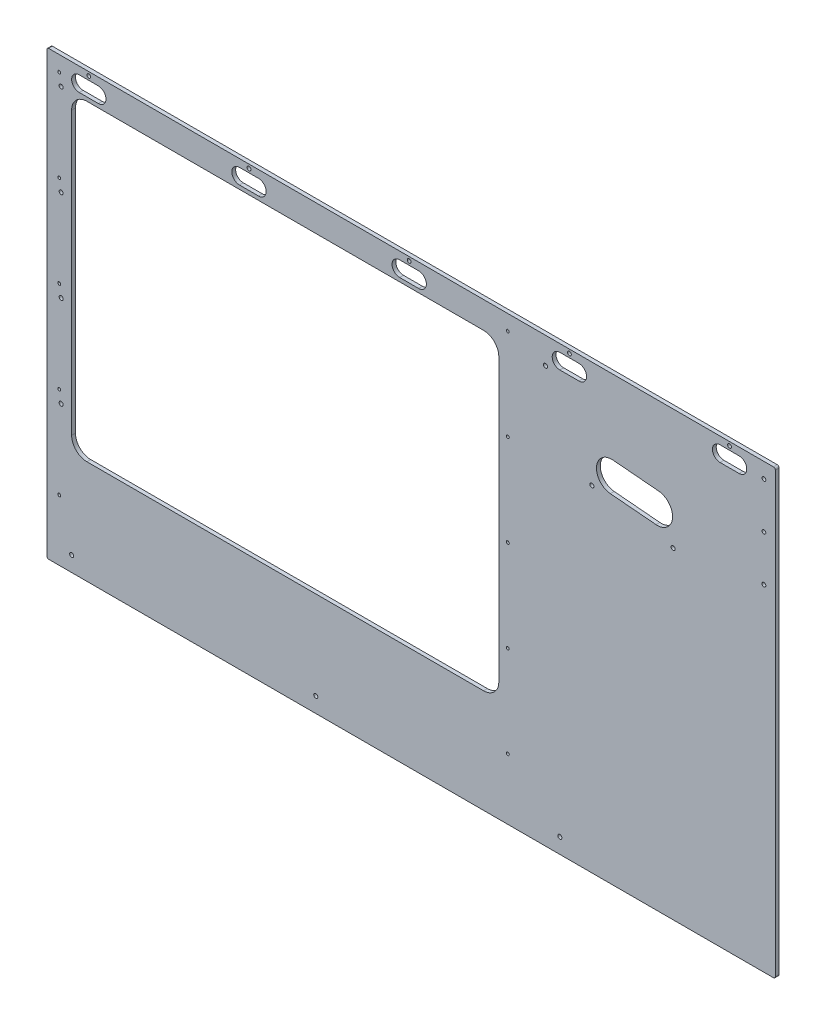
SolidWorks part; units mm, degrees
material "PC High Viscosity"
ref_plane "Front Plane" through (0, 0, 0) normal (0, 0, 1) x (1, 0, 0)
ref_plane "Top Plane" through (0, 0, 0) normal (0, 1, 0) x (1, 0, 0)
ref_plane "Right Plane" through (0, 0, 0) normal (1, 0, 0) x (0, 0, -1)
sketch "Sketch1" plane through (0, 0, 0) normal (0, 0, 1) x (1, 0, 0)
  line L1 (-606.425, -368.3) -> (606.425, -368.3)
  line L2 (-606.425, -368.3) -> (-606.425, 368.3)
  line L3 (-606.425, 368.3) -> (606.425, 368.3)
  line L4 (606.425, -368.3) -> (606.425, 368.3)
  line L5 (-606.425, -368.3) -> (606.425, 368.3) construction
  line L6 (-606.425, 368.3) -> (606.425, -368.3) construction
  point P0 (0, 0)
  dimension "D1" = 1212.85
  dimension "D2" = 736.6
extrude "Boss-Extrude1" add sketch "Sketch1" along normal blind 6.35
hole_wizard "H (0.266) Diameter Hole1" positions "Sketch3" profile "Sketch4" hole size "H" standard "ANSI Inch" end condition through all
sketch "Sketch3" plane through (0, 0, 6.35) normal (0, 0, 1) x (1, 0, 0)
  line L0 (-565.15, -342.9) -> (-158.75, -342.9) construction
  line L1 (-158.75, -342.9) -> (247.65, -342.9) construction
  line L3 (-606.425, -368.3) -> (606.425, -368.3) construction
  line L4 (-606.425, 368.3) -> (-606.425, -368.3) construction
  point P0 (-565.15, -342.9)
  point P2 (-158.75, -342.9)
  point P4 (247.65, -342.9)
  dimension "D1" = 25.4
  dimension "D2" = 406.4
  dimension "D3" = 41.275
sketch "Sketch4" plane through (-565.15, -342.9, 6.35) normal (1, 0, 0) x (0, -1, 0)
  line L0 (0, 0) -> (0, 6.35)
  line L1 (0, 6.35) -> (3.3782, 6.35)
  line L2 (3.3782, 6.35) -> (3.3782, 0)
  line L5 (3.3782, 0) -> (0, 0)
  line L11 (0, -6.35) -> (0, 107.95) construction
  dimension "Thru Hole Dia." = 6.7564
  dimension "Thru Hole Depth" = 6.35
sketch "Sketch2" plane through (0, 0, 6.35) normal (0, 0, 1) x (1, 0, 0)
  line L0 (606.425, 368.3) -> (-606.425, 368.3) construction
  line L1 (-565.15, 323.85) -> (146.05, 323.85)
  line L2 (-565.15, 323.85) -> (-565.15, -195.834)
  line L3 (-565.15, -195.834) -> (146.05, -195.834)
  line L4 (146.05, 323.85) -> (146.05, -195.834)
  line L5 (-585.7875, 342.9) -> (-585.7875, 190.5) construction
  line L6 (-606.425, 368.3) -> (-606.425, -368.3) construction
  line L7 (-585.7875, 190.5) -> (-585.7875, 38.1) construction
  line L8 (-585.7875, 38.1) -> (-585.7875, -114.3) construction
  line L9 (-585.7875, -114.3) -> (-585.7875, -266.7) construction
  circle A0 centre (-585.7875, 342.9) radius 2.4575
  circle A1 centre (-585.7875, 190.5) radius 2.4575
  circle A2 centre (-585.7875, 38.1) radius 2.4575
  circle A3 centre (-585.7875, -114.3) radius 2.4575
  circle A4 centre (-585.7875, -266.7) radius 2.4575
  circle A5 centre (160.9725, -266.7) radius 2.4575
  circle A6 centre (160.9725, -114.3) radius 2.4575
  circle A7 centre (160.9725, 38.1) radius 2.4575
  circle A8 centre (160.9725, 190.5) radius 2.4575
  circle A9 centre (160.9725, 342.9) radius 2.4575
  dimension "D8" = 4.9149
  dimension "D1" = 44.45
  dimension "D3" = 519.684
  dimension "D4" = 711.2
  dimension "D2" = 41.275
  dimension "D5" = 25.4
  dimension "D6" = 20.6375
  dimension "D7" = 152.4
  dimension "D9" = 746.76
extrude "Cut-Extrude1" cut sketch "Sketch2" against normal through all
hole_wizard "H (0.266) Diameter Hole2" positions "Sketch5" profile "Sketch6" hole size "H" standard "ANSI Inch" end condition through all
sketch "Sketch5" plane through (0, 0, 6.35) normal (0, 0, 1) x (1, 0, 0)
  line L0 (-582.6125, 323.596) -> (-582.6125, 171.196) construction
  line L1 (-582.6125, 171.196) -> (-582.6125, 18.796) construction
  line L2 (-582.6125, 18.796) -> (-582.6125, -133.604) construction
  line L5 (606.425, 368.3) -> (-606.425, 368.3) construction
  line L13 (-606.425, 368.3) -> (-606.425, -368.3) construction
  point P0 (-582.6125, 323.596)
  point P2 (-582.6125, 171.196)
  point P4 (-582.6125, 18.796)
  point P6 (-582.6125, -133.604)
  dimension "D1" = 23.8125
  dimension "D2" = 44.704
  dimension "D3" = 152.4
sketch "Sketch6" plane through (-582.6125, 323.596, 6.35) normal (1, 0, 0) x (0, -1, 0)
  line L0 (0, 0) -> (0, 6.35)
  line L1 (0, 6.35) -> (3.3782, 6.35)
  line L2 (3.3782, 6.35) -> (3.3782, 0)
  line L5 (3.3782, 0) -> (0, 0)
  line L11 (0, -6.35) -> (0, 107.95) construction
  dimension "Thru Hole Dia." = 6.7564
  dimension "Thru Hole Depth" = 6.35
hole_wizard "H (0.266) Diameter Hole3" positions "Sketch8" profile "Sketch9" hole size "H" standard "ANSI Inch" end condition through all
sketch "Sketch8" plane through (0, 0, 6.35) normal (0, 0, 1) x (1, 0, 0)
  line L5 (223.7708, 324.3059) -> (301.0598, 190.4374) construction
  line L6 (301.0598, 190.4374) -> (436.1577, 167.7114) construction
  line L9 (606.425, 368.3) -> (-606.425, 368.3) construction
  line L10 (606.425, -368.3) -> (606.425, 368.3) construction
  point P0 (223.7708, 324.3059)
  point P3 (223.7708, 324.3059)
  point P9 (436.1577, 167.7114)
  point P32 (301.0598, 190.4374)
  dimension "D1" = 9.549
  dimension "D2" = 43.9941
  dimension "D3" = 154.578
  dimension "D4" = 136.9961
  dimension "D5" = 382.6542
  dimension "D6" = 60
sketch "Sketch9" plane through (223.7708, 324.3059, 6.35) normal (1, 0, 0) x (0, -1, 0)
  line L0 (0, 0) -> (0, 6.35)
  line L1 (0, 6.35) -> (3.3782, 6.35)
  line L2 (3.3782, 6.35) -> (3.3782, 0)
  line L5 (3.3782, 0) -> (0, 0)
  line L11 (0, -6.35) -> (0, 107.95) construction
  dimension "Thru Hole Dia." = 6.7564
  dimension "Thru Hole Depth" = 6.35
sketch "Sketch12" plane through (0, 0, 6.35) normal (0, 0, 1) x (1, 0, 0)
  line L0 (-606.425, 361.95) -> (-536.575, 361.95) construction
  line L1 (-606.425, 368.3) -> (-606.425, -368.3) construction
  line L2 (606.425, 368.3) -> (-606.425, 368.3) construction
  line L3 (-552.45, 342.9) -> (-520.7, 342.9) construction
  line L4 (-552.45, 355.6) -> (-520.7, 355.6)
  line L5 (-552.45, 330.2) -> (-520.7, 330.2)
  circle A0 centre (-536.575, 361.95) radius 3.175
  arc A1 (-552.45, 355.6) -> (-552.45, 330.2) centre (-552.45, 342.9) ccw
  arc A2 (-520.7, 330.2) -> (-520.7, 355.6) centre (-520.7, 342.9) ccw
  point P9 (-536.575, 342.9)
  dimension "D3" = 6.35
  dimension "D5" = 12.7
  dimension "D1" = 69.85
  dimension "D2" = 6.35
  dimension "D4" = 31.75
  dimension "D6" = 19.05
extrude "Cut-Extrude4" cut sketch "Sketch12" against normal through all
pattern_linear "LPattern1" count 5 spacing 266.7 along (1, 0, 0) of "Cut-Extrude4"
fillet "Fillet1" radius 3.175 4 edges at (606.425, -368.3, 3.175) (606.425, 368.3, 3.175) (-606.425, -368.3, 3.175) (-606.425, 368.3, 3.175)
sketch "Sketch14" plane through (0, 0, 6.35) normal (0, 0, 1) x (1, 0, 0)
  line L0 (603.25, 368.3) -> (-603.25, 368.3) construction
  line L1 (371.9822, 215.9) -> (371.9822, 368.3) construction
  line L2 (334.0272, 219.2206) -> (409.9372, 212.5794) construction
  line L3 (336.2409, 244.524) -> (412.1509, 237.8827)
  line L4 (331.8134, 193.9173) -> (407.7234, 187.276)
  line L6 (606.425, -365.125) -> (606.425, 365.125) construction
  arc A1 (336.2409, 244.524) -> (331.8134, 193.9173) centre (334.0272, 219.2206) ccw
  arc A2 (407.7234, 187.276) -> (412.1509, 237.8827) centre (409.9372, 212.5794) ccw
  point P2 (371.9822, 215.9)
  dimension "D1" = 25.4
  dimension "D2" = 76.2
  dimension "D3" = 5
  dimension "D4" = 152.4
  dimension "D5" = 234.4428
extrude "Cut-Extrude5" cut sketch "Sketch14" against normal through all
hole_wizard "1/4 (0.25) Diameter Hole1" positions "Sketch15" profile "Sketch16" hole size "1/4" standard "ANSI Inch" end condition through all
sketch "Sketch15" plane through (0, 0, 6.35) normal (0, 0, 1) x (1, 0, 0)
  line L0 (606.425, -365.125) -> (606.425, 365.125) construction
  line L1 (603.25, 368.3) -> (-603.25, 368.3) construction
  point P2 (587.375, 342.9)
  point P6 (587.375, 266.7)
  point P10 (587.375, 190.5)
  dimension "D1" = 76.2
  dimension "D2" = 76.2
  dimension "D4" = 19.05
  dimension "D5" = 25.4
sketch "Sketch16" plane through (587.375, 342.9, 6.35) normal (1, 0, 0) x (0, -1, 0)
  line L0 (0, 0) -> (0, 6.35)
  line L1 (0, 6.35) -> (3.175, 6.35)
  line L2 (3.175, 6.35) -> (3.175, 0)
  line L5 (3.175, 0) -> (0, 0)
  line L11 (0, -6.35) -> (0, 107.95) construction
  dimension "Thru Hole Dia." = 6.35
  dimension "Thru Hole Depth" = 6.35
fillet "Fillet2" radius 25.4 4 edges at (146.05, 323.85, 3.175) (146.05, -195.834, 3.175) (-565.15, -195.834, 3.175) (-565.15, 323.85, 3.175)
equation "\"D6@Sketch2\"=\"D2@Sketch2\"/2"
